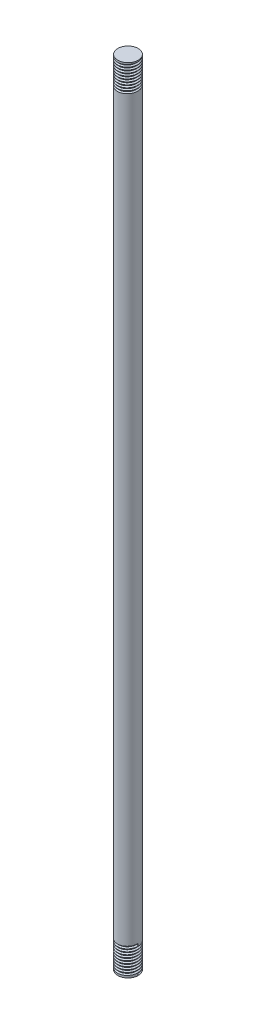
SolidWorks part; units mm, degrees
ref_plane "Front Plane" through (0, 0, 0) normal (0, 0, 1) x (1, 0, 0)
ref_plane "Top Plane" through (0, 0, 0) normal (0, 1, 0) x (1, 0, 0)
ref_plane "Right Plane" through (0, 0, 0) normal (1, 0, 0) x (0, 0, -1)
sketch "Sketch1" plane through (0, 0, 0) normal (0, 1, 0) x (1, 0, 0)
  circle A0 centre (0, 0) radius 4
  dimension "D1" = 8
extrude "Boss-Extrude1" add sketch "Sketch1" along normal blind 310
thread "Thread1" pitch 1 method cut profile "Thread Profile1" start angle 0, offset 0, length 10, pitch 1, diameter 8
ref_plane "Plane1" through (-4, 310, 0) normal (0, 0, 1) x (-1, 0, 0)
sketch "Thread Profile1" plane through (-4, 310, 0) normal (0, 0, 1) x (-1, 0, 0)
  line L0 (0, 0) -> (0, 1) construction
  line L11 (0, 0) -> (0, 0.875)
  line L12 (0, 0.875) -> (-0.5413, 0.5625)
  line L13 (-0.5413, 0.5625) -> (-0.5413, 0.3125)
  line L15 (-0.5413, 0.3125) -> (0, 0)
  line L17 (-0.5413, 0.4375) -> (0, 0.4375) construction
  point P2 (0, 0)
  dimension "Pitch" = 1
  dimension "Profile_Angle" = 60
  dimension "Profile_Land" = 0.25
  dimension "Profile_Height" = 0.5413
thread "Thread2" pitch 1 method cut profile "Thread Profile2" start angle 0, offset 0, length 10, pitch 1, diameter 8
ref_plane "Plane2" through (4, 0, 0) normal (0, 0, 1) x (1, 0, 0)
sketch "Thread Profile2" plane through (4, 0, 0) normal (0, 0, 1) x (1, 0, 0)
  line L0 (0, 0) -> (0, 1) construction
  line L11 (0, 0) -> (0, 0.875)
  line L12 (0, 0.875) -> (-0.5413, 0.5625)
  line L13 (-0.5413, 0.5625) -> (-0.5413, 0.3125)
  line L15 (-0.5413, 0.3125) -> (0, 0)
  line L17 (-0.5413, 0.4375) -> (0, 0.4375) construction
  point P2 (0, 0)
  dimension "Pitch" = 1
  dimension "Profile_Angle" = 60
  dimension "Profile_Land" = 0.25
  dimension "Profile_Height" = 0.5413
